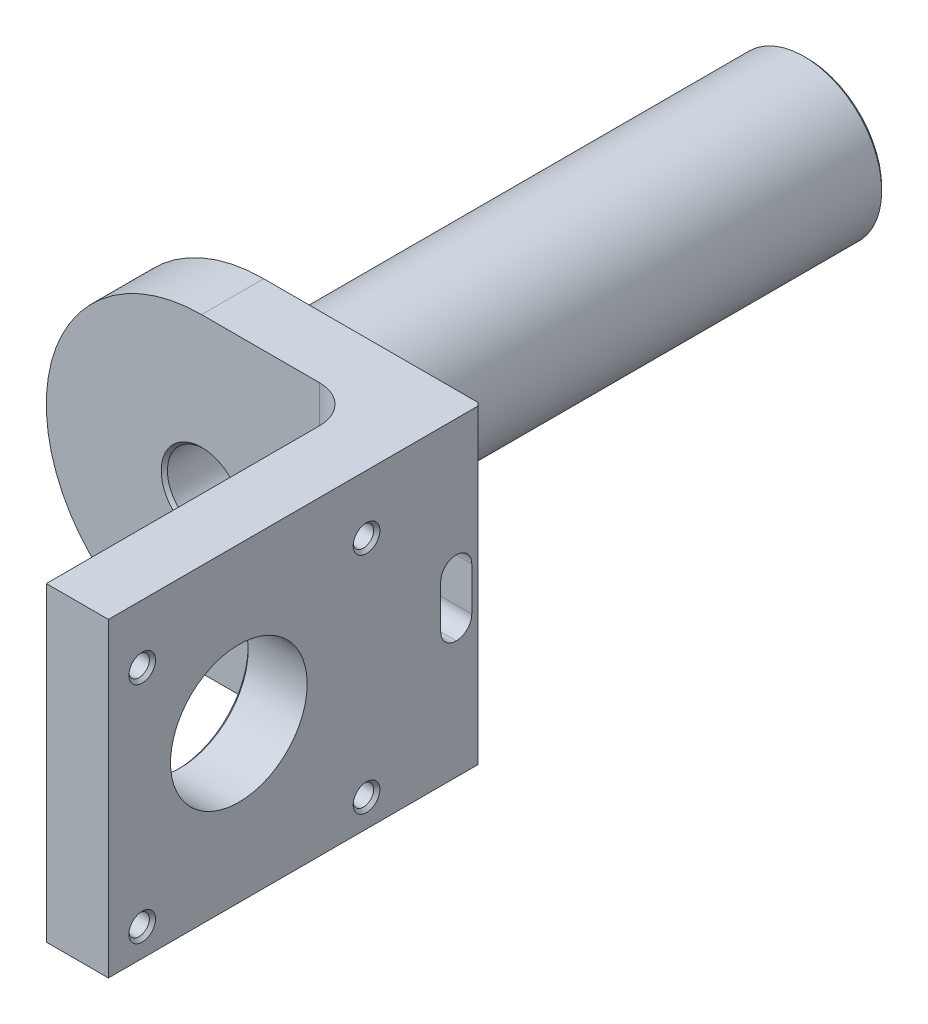
SolidWorks part; units mm, degrees
ref_plane "Ebene vorne" through (0, 0, 0) normal (0, 0, 1) x (1, 0, 0)
ref_plane "Ebene oben" through (0, 0, 0) normal (0, 1, 0) x (1, 0, 0)
ref_plane "Ebene rechts" through (0, 0, 0) normal (1, 0, 0) x (0, 0, -1)
sketch "Skizze1" plane through (0, 0, 0) normal (0, 0, 1) x (1, 0, 0)
  circle A0 centre (0, 0) radius 12.5
  circle A1 centre (0, 0) radius 6
  dimension "D1" = 25
extrude "Aufsatz-Linear austragen1" add sketch "Skizze1" along normal blind 86.5
sketch "Skizze2" plane through (0, 0, 86.5) normal (0, 0, 1) x (1, 0, 0)
  circle A0 centre (0, 0) radius 6
  circle A1 centre (0, 0) radius 14.25
  dimension "D1" = 28.5
extrude "Aufsatz-Linear austragen2" add sketch "Skizze2" along normal blind 1
sketch "Skizze3" plane through (0, 0, 0) normal (0, 0, -1) x (-1, 0, 0)
  line L0 (6, 0) -> (12.5, 0) construction
  circle A0 centre (0, 0) radius 6
  circle A1 centre (0, 0) radius 12.5
  circle A2 centre (9.25, 0) radius 1.65
  circle A3 centre (4.625, -8.0107) radius 1.65
  circle A4 centre (-4.625, -8.0107) radius 1.65
  circle A5 centre (-9.25, 0) radius 1.65
  circle A6 centre (-4.625, 8.0107) radius 1.65
  circle A7 centre (4.625, 8.0107) radius 1.65
  point P20 (0, 0)
  dimension "D1" = 6
extrude "Schnitt-Linear austragen1" cut sketch "Skizze3" against normal blind 15 contours A7 | A2 L0 | L0 A2 | A3 | A4 | A5 | A6 region at (-9.25, -0.7003, 0) region at (-9.25, 0.7003, 0) region at (-4.625, -8.0107, 0) region at (4.625, -8.0107, 0) region at (9.25, 0, 0) region at (-4.625, 8.0107, 0)
sketch "Skizze4" plane through (0, 0, 87.5) normal (0, 0, 1) x (1, 0, 0)
  line L1 (-25, -25) -> (25, -25)
  line L2 (-25, -25) -> (-25, 25)
  line L3 (-25, 25) -> (25, 25)
  line L4 (25, -25) -> (25, 25)
  line L5 (-25, -25) -> (25, 25) construction
  line L6 (-25, 25) -> (25, -25) construction
  circle A0 centre (0, 0) radius 6
  circle A1 centre (0, 0) radius 25
  circle A2 centre (0, 0) radius 6
  point P0 (0, 0)
  circle M5 centre (0, 0) radius 14.25
  circle M6 centre (0, 0) radius 6
  dimension "D1" = 50
  dimension "D2" = 50
extrude "Aufsatz-Linear austragen3" add sketch "Skizze4" along normal blind 10 contours M5 M6 | A1 M5 | A1 L4 L3 | A1 L1 L4 region at (19.4158, -19.4158, 87.5) region at (-17.1777, -17.1777, 87.5) region at (19.4158, 19.4158, 87.5) region at (-13.8469, 0, 87.5)
sketch "Skizze5" plane through (25, 0, 0) normal (1, 0, 0) x (0, 0, -1)
  line L0 (-147.5, 0) -> (-87.5, 0) construction
  line L1 (-87.5, 25) -> (-147.5, 25)
  line L2 (-87.5, 25) -> (-87.5, -25)
  line L3 (-87.5, -25) -> (-147.5, -25)
  line L4 (-147.5, 25) -> (-147.5, -25)
  line L5 (-87.5, 25) -> (-147.5, -25) construction
  line L6 (-87.5, -25) -> (-147.5, 25) construction
  line L7 (-97.5, -25) -> (-87.5, -25) construction
  line L9 (-105.5, 21) -> (-147.5, 21)
  line L10 (-105.5, 21) -> (-105.5, -21)
  line L11 (-105.5, -21) -> (-147.5, -21)
  line L12 (-147.5, 21) -> (-147.5, -21)
  line L13 (-105.5, 21) -> (-147.5, -21) construction
  line L14 (-105.5, -21) -> (-147.5, 21) construction
  line L15 (-97.5, -25) -> (-97.5, 25) construction
  circle A0 centre (-126.5, 0) radius 11
  circle A1 centre (-126.5, 0) radius 22
  circle A2 centre (-142.0563, 15.5563) radius 1.65
  circle A3 centre (-105.9437, 15.5563) radius 1.65
  circle A4 centre (-105.9437, -20.5563) radius 1.65
  circle A5 centre (-142.0563, -20.5563) radius 1.65
  point P4 (-117.5, 0)
  point P10 (-126.5, 0)
  point P29 (-124, -2.5)
  line M15 (-87.5, 25) -> (-97.5, 25)
  line M17 (-97.5, -25) -> (-87.5, -25)
  dimension "D4" = 22
  dimension "D5" = 44
  dimension "D6" = 4
  dimension "D1" = 42
  dimension "D2" = 42
  dimension "D3" = 50
extrude "Aufsatz-Linear austragen4" add sketch "Skizze5" along normal blind 10 contours M17 M15 | A1 L9 L10 L11 L4 L3 L1 | L9 A1 | A3 A1 L10 L9 | A5 A1 L11 A4 L10 A3 L9 A2 L12 A0 | A2 A1 L9 L4 | A5 A1 L4 L11 | L11 A1 | A4 A1 L11 L10 | L10 A1 region at (25, 0.0974, 104.2394) region at (25, 17.0931, 143.5931) region at (25, 10.3849, 145.2182) region at (25, 21.4008, 126.5) region at (25, -16.7536, 143.6593) region at (25, 17.1593, 109.7464) region at (25, -21.4008, 126.5) region at (25, 0, 105.0992) region at (25, -16.8536, 109.6464)
fillet "Verrundung1" radius 6 1 edges at (25, 0, 97.5)
chamfer "Fase1" distance 0.5 angle 45 15 edges at (25, 0, 115.5) (2.975, 8.0107, 0) (7.6, 0, 0) (2.975, -8.0107, 0) (-6.275, -8.0107, 0) (-10.9, 0, 0) (6, 0, 0) (-6.275, 8.0107, 0) (12.5, 0, 0) (6, 0, 97.5) (35, 15.5563, 140.4063) (35, -20.5563, 140.4063) (35, 15.5563, 104.2937) (35, -20.5563, 104.2937) (35, 0, 87.5)
sketch "Skizze6" plane through (35, 0, 0) normal (1, 0, 0) x (0, 0, -1)
  line L0 (-88, 0) -> (-95.854, 0) construction
  line L2 (-88, -25) -> (-88, 25) construction
  line L8 (-94, 6) -> (-89, 6)
  line L9 (-94, 6) -> (-94, -6)
  line L10 (-94, -6) -> (-89, -6)
  line L11 (-89, 6) -> (-89, -6)
  line L12 (-94, 6) -> (-89, -6) construction
  line L13 (-94, -6) -> (-89, 6) construction
  point P5 (-91.5, 0)
  dimension "D1" = 1
  dimension "D2" = 5
  dimension "D3" = 12
extrude "Schnitt-Linear austragen2" cut sketch "Skizze6" against normal blind 35
fillet "Verrundung2" radius 2.5 6 edges at (6, 0, 94) (6, 0, 89) (17.5, -6, 89) (17.5, -6, 94) (17.5, 6, 94) (17.5, 6, 89)
